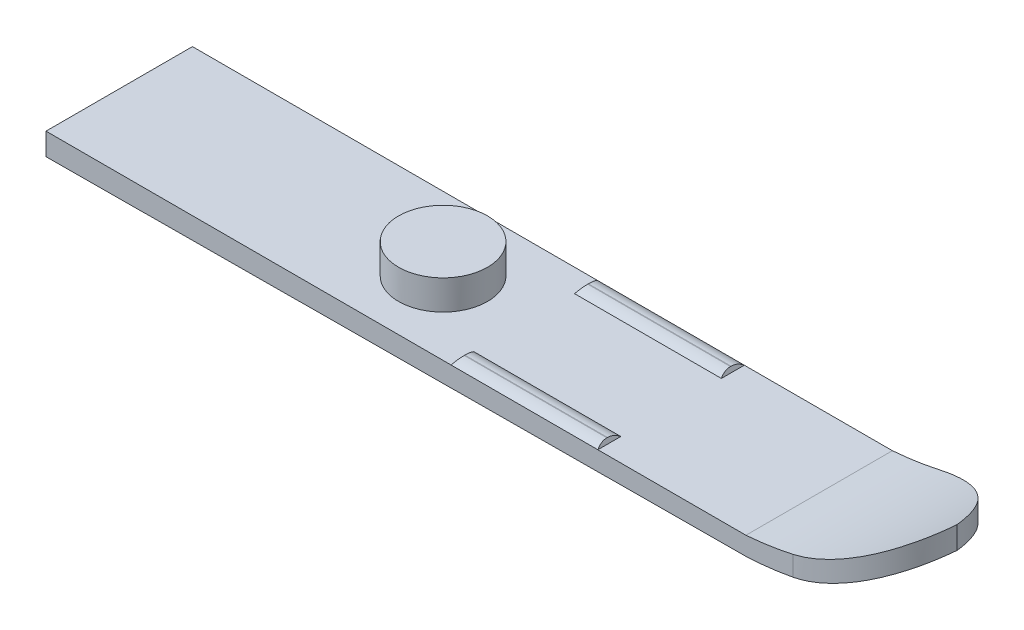
SolidWorks part; units mm, degrees
ref_plane "Front Plane" through (0, 0, 0) normal (0, 0, 1) x (1, 0, 0)
ref_plane "Top Plane" through (0, 0, 0) normal (0, 1, 0) x (1, 0, 0)
ref_plane "Right Plane" through (0, 0, 0) normal (1, 0, 0) x (0, 0, -1)
sketch "Sketch1" plane through (0, 0, 0) normal (0, 0, 1) x (1, 0, 0)
  line L0 (-20.3715, 0.0138) -> (17.388, 0.2225)
  line L2 (-20.3715, 1.2097) -> (17.388, 1.2097)
  line L3 (24.9383, 2.3032) -> (24.9383, 3.5143)
  line L4 (-20.3715, 0.0138) -> (-20.3715, 1.2097)
  arc A0 (17.388, 0.2225) -> (24.9383, 2.3032) centre (16.654, 17.6261) ccw
  arc A1 (17.388, 1.2097) -> (24.9383, 3.5143) centre (16.0206, 19.2104) ccw
extrude "SkateBoardBase" add sketch "Sketch1" along normal blind 7.9
fillet "CurvedFront" radius 5 2 edges at (24.9383, 2.9087, 0) (24.9383, 2.9087, 7.9)
ref_plane "Plane1" through (0, 1.2097, 0) normal (0, 1, 0) x (1, 0, 0)
sketch "Sketch2" plane through (0, 1.2097, 0) normal (0, 1, 0) x (1, 0, 0)
  line L0 (-22.8617, -3.95) -> (-2.902, -3.95) construction
  circle A0 centre (-2.902, -3.95) radius 2.4
  point P5 (0, 0)
  dimension "D1" = 4.8
extrude "Stud" add sketch "Sketch2" along normal blind 1.6
sketch "Sketch3" plane through (0, 1.2097, 0) normal (0, 1, 0) x (1, 0, 0)
  line L0 (-0.502, -3.95) -> (1.4776, -3.95) construction
  line L1 (1.4776, -3.95) -> (1.4776, 0) construction
  line L2 (17.388, 0) -> (-20.3715, 0) construction
  line L3 (1.4776, -3.95) -> (1.4776, -7.9) construction
  line L4 (17.388, -7.9) -> (-20.3715, -7.9) construction
  line L5 (1.4776, 0) -> (1.4776, -1.2369)
  line L6 (1.4776, -1.2369) -> (9.3998, -1.2369)
  line L7 (9.3998, -1.2369) -> (9.3998, 0)
  line L8 (9.3998, 0) -> (1.4776, 0)
  line L9 (9.3998, -6.6631) -> (9.3998, -7.9)
  line L10 (1.4776, -6.6631) -> (9.3998, -6.6631)
  line L11 (1.4776, -7.9) -> (1.4776, -6.6631)
  line L12 (9.3998, -7.9) -> (1.4776, -7.9)
  circle A0 centre (-2.902, -3.95) radius 2.4 construction
  circle A1 centre (-2.902, -3.95) radius 2.4 construction
extrude "UpperNotches" add sketch "Sketch3" along normal blind 0.2 draft 30
fillet "NotchFillet" radius 1 4 edges at (5.4387, 1.4097, 1.1215) (5.4387, 1.4097, 0.1155) (5.4387, 1.4097, 7.7845) (5.4387, 1.4097, 6.7785)
ref_plane "Plane2" through (-0.0007, 0.1264, 0) normal (0.0055, -1, 0) x (-1, -0.0055, 0)
sketch "Sketch4" plane through (-0.0007, 0.1264, 0) normal (0.0055, -1, 0) x (-1, -0.0055, 0)
  circle A0 centre (2.8953, -3.95) radius 1.2
  dimension "D1" = 2.4
extrude "UnderStudHole" cut sketch "Sketch4" against normal blind 1.6
